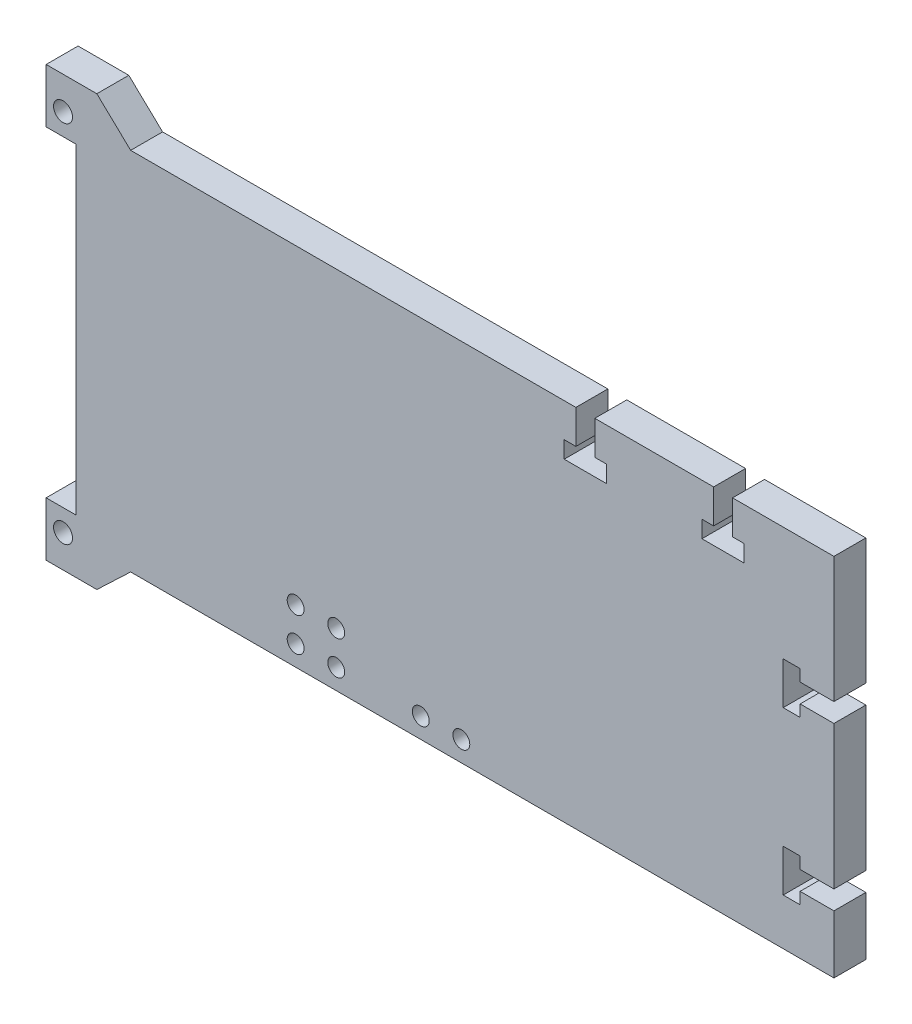
SolidWorks part; units mm, degrees
ref_plane "Front Plane" through (0, 0, 0) normal (0, 0, 1) x (1, 0, 0)
ref_plane "Top Plane" through (0, 0, 0) normal (0, 1, 0) x (1, 0, 0)
ref_plane "Right Plane" through (0, 0, 0) normal (1, 0, 0) x (0, 0, -1)
sketch "Sketch1" plane through (0, 0, 0) normal (0, 0, 1) x (1, 0, 0)
  line L1 (0, 0) -> (142.367, 0)
  line L2 (0, 0) -> (0, 68.58)
  line L3 (0, 68.58) -> (142.367, 68.58)
  line L4 (142.367, 0) -> (142.367, 68.58)
  dimension "D1" = 142.367
  dimension "D2" = 68.58
extrude "Boss-Extrude1" add sketch "Sketch1" along normal blind 6
sketch "Sketch2" plane through (0, 0, 6) normal (0, 0, 1) x (1, 0, 0)
  line L1 (0, 68.58) -> (-5.588, 68.58)
  line L2 (0, 68.58) -> (0, 64.4525)
  line L3 (0, 64.4525) -> (-5.588, 64.4525)
  line L4 (-5.588, 68.58) -> (-5.588, 64.4525)
  line L5 (0, 0) -> (-5.588, 0)
  line L6 (0, 0) -> (0, 4.1275)
  line L7 (0, 4.1275) -> (-5.588, 4.1275)
  line L8 (-5.588, 0) -> (-5.588, 4.1275)
  dimension "D1" = 5.588
  dimension "D2" = 60.325
extrude "Boss-Extrude2" add sketch "Sketch2" against normal up to surface (6 mm away) up to face at (71.1835, 34.29, 0)
sketch "Sketch3" plane through (0, 0, 6) normal (0, 0, 1) x (1, 0, 0)
  line L0 (0, 68.58) -> (0, 72.39)
  line L1 (142.367, 68.58) -> (-5.588, 68.58) construction
  line L2 (0, 72.39) -> (2.54, 72.39)
  line L3 (2.54, 72.39) -> (9.525, 68.58)
  line L4 (9.525, 68.58) -> (0, 68.58)
  line L5 (0, 0) -> (0, -3.81)
  line L6 (0, -3.81) -> (2.54, -3.81)
  line L7 (2.54, -3.81) -> (9.525, 0)
  line L8 (-5.588, 0) -> (142.367, 0) construction
  line L9 (9.525, 0) -> (0, 0)
  dimension "D1" = 3.81
  dimension "D2" = 2.54
  dimension "D3" = 9.525
extrude "Boss-Extrude3" add sketch "Sketch3" against normal up to surface (6 mm away) up to face at (32.4485, 38.0603, 0)
sketch "Sketch4" plane through (0, 0, 6) normal (0, 0, 1) x (1, 0, 0)
  line L0 (142.367, 0) -> (142.367, 68.58) construction
  line L1 (142.367, 44.958) -> (136.017, 44.958)
  line L2 (142.367, 44.958) -> (142.367, 41.402)
  line L3 (142.367, 41.402) -> (136.017, 41.402)
  line L4 (136.017, 44.958) -> (136.017, 41.402) construction
  line L5 (136.017, 44.958) -> (136.017, 47.1487)
  line L6 (142.367, 14.478) -> (136.017, 14.478)
  line L7 (142.367, 14.478) -> (142.367, 10.922)
  line L8 (142.367, 10.922) -> (136.017, 10.922)
  line L9 (136.017, 14.478) -> (136.017, 10.922) construction
  line L10 (136.017, 47.1487) -> (132.842, 47.1487)
  line L11 (132.842, 47.1487) -> (132.842, 39.2112)
  line L12 (132.842, 39.2112) -> (136.017, 39.2112)
  line L13 (136.017, 39.2112) -> (136.017, 41.402)
  line L14 (136.017, 14.478) -> (136.017, 16.6688)
  line L15 (136.017, 16.6688) -> (132.842, 16.6688)
  line L16 (132.842, 16.6688) -> (132.842, 8.7313)
  line L17 (132.842, 8.7313) -> (136.017, 8.7313)
  line L18 (136.017, 8.7313) -> (136.017, 10.922)
  line L19 (132.842, 43.18) -> (142.367, 43.18) construction
  line L20 (132.842, 12.7) -> (142.367, 12.7) construction
  line L21 (142.367, 68.58) -> (9.525, 68.58) construction
  line L22 (9.525, 0) -> (142.367, 0) construction
  line L23 (93.9038, 62.23) -> (91.713, 62.23)
  line L24 (123.3322, 68.58) -> (119.7762, 68.58)
  line L25 (123.3322, 68.58) -> (123.3322, 62.23)
  line L26 (123.3322, 62.23) -> (119.7762, 62.23) construction
  line L27 (119.7762, 68.58) -> (119.7762, 62.23)
  line L28 (97.4598, 68.58) -> (93.9038, 68.58)
  line L29 (97.4598, 68.58) -> (97.4598, 62.23)
  line L30 (97.4598, 62.23) -> (93.9038, 62.23) construction
  line L31 (93.9038, 68.58) -> (93.9038, 62.23)
  line L32 (91.713, 62.23) -> (91.713, 59.055)
  line L33 (91.713, 59.055) -> (99.6505, 59.055)
  line L34 (99.6505, 59.055) -> (99.6505, 62.23)
  line L35 (99.6505, 62.23) -> (97.4598, 62.23)
  line L36 (119.7762, 62.23) -> (117.5855, 62.23)
  line L37 (117.5855, 62.23) -> (117.5855, 59.055)
  line L38 (117.5855, 59.055) -> (125.523, 59.055)
  line L39 (125.523, 59.055) -> (125.523, 62.23)
  line L40 (125.523, 62.23) -> (123.3322, 62.23)
  line L41 (95.6818, 59.055) -> (95.6818, 68.58) construction
  line L42 (121.5542, 59.055) -> (121.5542, 68.58) construction
  dimension "D1" = 25.4
  dimension "D2" = 12.7
  dimension "D3" = 7.9375
  dimension "D4" = 3.175
  dimension "D5" = 6.35
  dimension "D6" = 3.556
  dimension "D7" = 20.8128
  dimension "D8" = 46.6852
extrude "Cut-Extrude1" cut sketch "Sketch4" against normal through all
sketch "Sketch5" plane through (0, 0, 6) normal (0, 0, 1) x (1, 0, 0)
  line L0 (10.287, 0) -> (3.937, -6.0325)
  line L1 (-5.588, 68.58) -> (10.287, 68.58)
  line L2 (-5.588, 68.58) -> (-5.588, 74.6125)
  line L3 (-5.588, 74.6125) -> (10.287, 74.6125) construction
  line L4 (10.287, 68.58) -> (10.287, 74.6125) construction
  line L5 (-5.588, 0) -> (10.287, 0)
  line L6 (-5.588, 0) -> (-5.588, -6.0325)
  line L7 (-5.588, -6.0325) -> (10.287, -6.0325) construction
  line L8 (10.287, 0) -> (10.287, -6.0325) construction
  line L9 (3.937, -6.0325) -> (-5.588, -6.0325)
  line L10 (10.287, 68.58) -> (3.937, 74.6125)
  line L11 (3.937, 74.6125) -> (-5.588, 74.6125)
  dimension "D1" = 80.645
  dimension "D2" = 15.875
  dimension "D3" = 9.525
extrude "Boss-Extrude4" add sketch "Sketch5" against normal up to surface (6 mm away) up to face at (87.6463, 42.3796, 0)
sketch "Sketch6" plane through (0, 0, 6) normal (0, 0, 1) x (1, 0, 0)
  line L0 (-5.588, 68.5165) -> (-2.413, 68.5165) construction
  line L1 (41.275, 3.81) -> (41.275, 10.16) construction
  line L2 (-5.588, 0.0635) -> (-2.413, 0.0635) construction
  line L3 (41.275, 10.16) -> (48.895, 10.16) construction
  line L4 (48.895, 3.81) -> (64.77, 3.81) construction
  line L5 (64.77, 3.81) -> (72.39, 3.81) construction
  line L6 (10.287, 0) -> (142.367, 0) construction
  line L7 (41.275, 3.81) -> (48.895, 3.81) construction
  line L8 (48.895, 10.16) -> (48.895, 3.81) construction
  line L9 (-5.588, 64.4525) -> (0, 64.4525) construction
  line L10 (0, 4.1275) -> (-5.588, 4.1275) construction
  line L11 (-5.588, 74.6125) -> (-5.588, 64.4525) construction
  line L12 (-5.588, 4.1275) -> (-5.588, -6.0325) construction
  circle A0 centre (-2.413, 68.5165) radius 1.778
  circle A1 centre (-2.413, 0.0635) radius 1.778
  circle A2 centre (64.77, 3.81) radius 1.5875
  circle A3 centre (72.39, 3.81) radius 1.5875
  circle A4 centre (41.275, 3.81) radius 1.5875
  circle A5 centre (48.895, 3.81) radius 1.5875
  circle A6 centre (41.275, 10.16) radius 1.5875
  circle A7 centre (48.895, 10.16) radius 1.5875
  dimension "D1" = 3.556
  dimension "D4" = 15.875
  dimension "D3" = 3.175
  dimension "D2" = 3.175
  dimension "D5" = 41.275
  dimension "D6" = 3.81
  dimension "D7" = 7.62
  dimension "D8" = 4.064
  dimension "D9" = 4.064
  dimension "D10" = 6.35
extrude "Cut-Extrude2" cut sketch "Sketch6" against normal through all
sketch "Sketch7" plane through (0, 0, 6) normal (0, 0, 1) x (1, 0, 0)
  line L0 (119.7762, 68.58) -> (97.4598, 68.58) construction
  line L1 (91.713, 59.055) -> (99.6505, 59.055)
  line L2 (91.713, 59.055) -> (91.713, 68.58)
  line L3 (91.713, 68.58) -> (99.6505, 68.58) construction
  line L4 (99.6505, 59.055) -> (99.6505, 68.58)
  line L5 (142.367, 68.58) -> (123.3322, 68.58) construction
  line L6 (117.5855, 59.055) -> (125.523, 59.055)
  line L7 (117.5855, 59.055) -> (117.5855, 68.58)
  line L8 (117.5855, 68.58) -> (125.523, 68.58) construction
  line L9 (125.523, 59.055) -> (125.523, 68.58)
  line L10 (142.367, 44.958) -> (142.367, 68.58) construction
  line L11 (132.842, 39.2112) -> (142.367, 39.2112)
  line L12 (132.842, 39.2112) -> (132.842, 47.1487) construction
  line L13 (132.842, 47.1487) -> (142.367, 47.1487)
  line L14 (142.367, 39.2112) -> (142.367, 47.1487) construction
  line L15 (142.367, 14.478) -> (142.367, 41.402) construction
  line L16 (132.842, 8.7313) -> (142.367, 8.7313)
  line L17 (132.842, 8.7313) -> (132.842, 16.6688) construction
  line L18 (132.842, 16.6688) -> (142.367, 16.6688)
  line L19 (142.367, 8.7313) -> (142.367, 16.6688) construction
  line L20 (136.017, 47.1487) -> (132.842, 47.1487) construction
  line L21 (136.017, 16.6688) -> (132.842, 16.6688) construction
  line L22 (125.523, 59.055) -> (125.523, 62.23) construction
  line L23 (99.6505, 59.055) -> (99.6505, 62.23) construction
  line L24 (132.842, 12.7) -> (142.367, 12.7) construction
  line L25 (94.1832, 68.58) -> (97.1804, 68.58) construction
  line L26 (94.1832, 68.58) -> (94.1832, 62.23)
  line L27 (94.1832, 62.23) -> (97.1804, 62.23)
  line L28 (97.1804, 68.58) -> (97.1804, 62.23)
  line L29 (120.0556, 68.58) -> (123.0528, 68.58) construction
  line L30 (120.0556, 68.58) -> (120.0556, 62.23)
  line L31 (120.0556, 62.23) -> (123.0528, 62.23)
  line L32 (123.0528, 68.58) -> (123.0528, 62.23)
  line L33 (142.367, 44.6786) -> (132.842, 44.6786)
  line L34 (142.367, 44.6786) -> (142.367, 41.6814) construction
  line L35 (142.367, 41.6814) -> (132.842, 41.6814)
  line L36 (132.842, 44.6786) -> (132.842, 41.6814) construction
  line L37 (142.367, 14.1986) -> (132.842, 14.1986)
  line L38 (142.367, 14.1986) -> (142.367, 11.2014) construction
  line L39 (142.367, 11.2014) -> (132.842, 11.2014)
  line L40 (132.842, 14.1986) -> (132.842, 11.2014) construction
  line L41 (132.842, 43.18) -> (142.367, 43.18) construction
  line L42 (95.6818, 62.23) -> (95.6818, 68.58) construction
  line L43 (121.5542, 62.23) -> (121.5542, 68.58) construction
  line L44 (91.713, 68.58) -> (94.1832, 68.58)
  line L45 (97.1804, 68.58) -> (99.6505, 68.58)
  line L46 (117.5855, 68.58) -> (120.0556, 68.58)
  line L47 (123.0528, 68.58) -> (125.523, 68.58)
  line L48 (142.367, 47.1487) -> (142.367, 44.6786)
  line L49 (142.367, 41.6814) -> (142.367, 39.2112)
  line L50 (142.367, 16.6688) -> (142.367, 14.1986)
  line L51 (142.367, 11.2014) -> (142.367, 8.7313)
  line L52 (132.842, 44.6786) -> (132.842, 47.1487)
  line L53 (132.842, 41.6814) -> (132.842, 39.2112)
  line L54 (132.842, 16.6688) -> (132.842, 14.1986)
  line L55 (132.842, 11.2014) -> (132.842, 8.7313)
  dimension "D1" = 2.9972
  dimension "D2" = 6.35
  dimension "D3" = 9.525
extrude "Boss-Extrude5" [suppressed] add sketch "Sketch7" against normal up to surface (6 mm away) up to face at (47.3075, 10.16, 0)
chamfer "Chamfer1" [suppressed] distance 0.381 angle 70
fillet "Fillet1" [suppressed] radius 0.508
